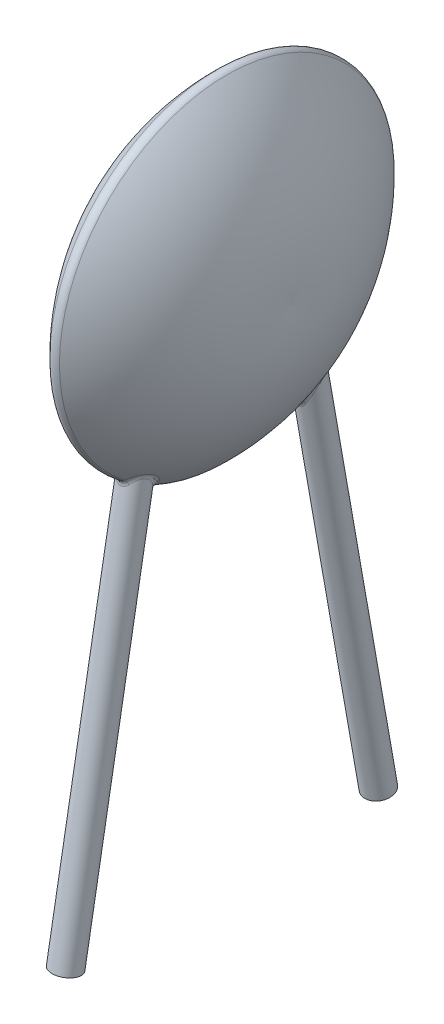
SolidWorks part; units mm, degrees
ref_plane "Front Plane" through (0, 0, 0) normal (0, 0, 1) x (1, 0, 0)
ref_plane "Top Plane" through (0, 0, 0) normal (0, 1, 0) x (1, 0, 0)
ref_plane "Right Plane" through (0, 0, 0) normal (1, 0, 0) x (0, 0, -1)
sketch "Sketch1" plane through (0, 0, 0) normal (0, 0, 1) x (1, 0, 0)
  line L0 (0, -4.6085) -> (0, 4.8852) construction
  line L1 (-5.737, 0) -> (6.7417, 0) construction
  line L2 (-1, 0) -> (1, 0)
  arc A1 (-1, 0) -> (0, 2.5) centre (2.0912, 0.2135) cw
  arc A2 (1, 0) -> (0, 2.5) centre (-2.0912, 0.2135) ccw
  dimension "D1" = 2.5
  dimension "D2" = 1
revolve "Revolve1" add sketch "Sketch1" angle 360 about L2
sketch "Sketch4" plane through (0, 0, 0) normal (0, 1, 0) x (1, 0, 0)
  line L0 (-3.9069, 0) -> (3.6967, 0) construction
fillet "Fillet1" radius 0.1 1 edges at (0, 0, 2.5)
ref_plane "Plane1" through (0, 0, 0) normal (0, -0.9848, -0.1736) x (1, 0, 0)
ref_plane "Plane2" through (0, -7.8785, -1.3892) normal (0, -0.9848, -0.1736) x (1, 0, 0)
sketch "Sketch5" plane through (0, -7.8785, -1.3892) normal (0, -0.9848, -0.1736) x (1, 0, 0)
  circle A0 centre (0, -0.9) radius 0.2
  dimension "D1" = 0.4
  dimension "D2" = 0.9
extrude "Boss-Extrude1" add sketch "Sketch5" against normal blind 8 contours A0
mirror "Mirror1" about plane through (0, 0, 0) normal (0, 0, 1) of "Boss-Extrude1"
fillet "Fillet2" radius 0.1 4 edges at (-0.0112, -2.2027, 1.0995) (-0.0105, -1.9783, 1.4655) (-0.1964, -1.9091, 1.289) (0.1972, -1.9108, 1.2849)
fillet "Fillet3" radius 0.1 4 edges at (-0.0112, -2.2027, -1.0995) (-0.0105, -1.9783, -1.4655) (-0.1964, -1.9091, -1.289) (0.1972, -1.9108, -1.2849)
